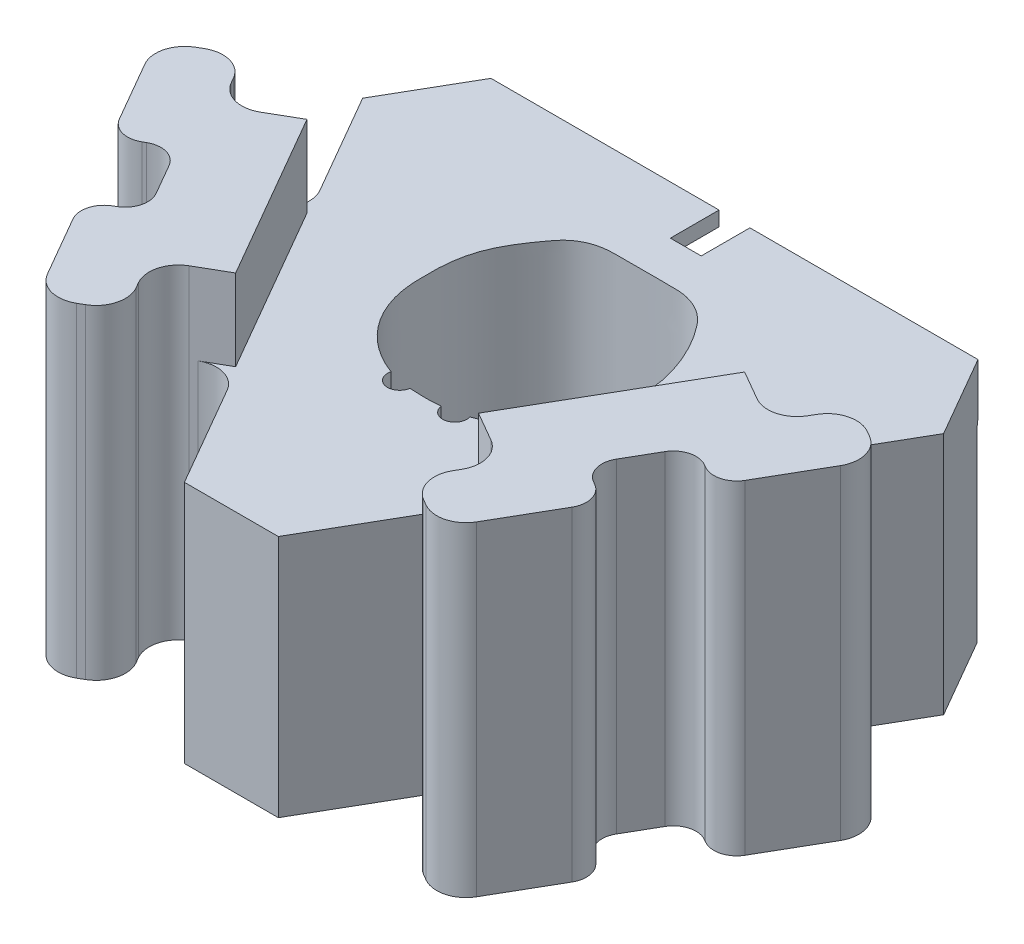
SolidWorks part; units mm, degrees
material "Nylon 101"
ref_plane "Plan de face" through (0, 0, 0) normal (0, 0, 1) x (1, 0, 0)
ref_plane "Plan de dessus" through (0, 0, 0) normal (0, 1, 0) x (1, 0, 0)
ref_plane "Plan de droite" through (0, 0, 0) normal (1, 0, 0) x (0, 0, -1)
sketch "Esquisse2" plane through (0, 0, 0) normal (0, 1, 0) x (1, 0, 0)
  line L5 (0, 0) -> (0, 12) construction
  line L6 (15, 12) -> (-15, 12)
  line L10 (2.8923, -18.9904) -> (17.8923, 6.9904)
  line L11 (0, 0) -> (10.3923, -6) construction
  line L12 (-17.8923, 6.9904) -> (-2.8923, -18.9904)
  line L13 (0, 0) -> (-10.3923, -6) construction
  line L14 (-15, 12) -> (-17.8923, 6.9904)
  line L15 (-2.8923, -18.9904) -> (2.8923, -18.9904)
  line L16 (17.8923, 6.9904) -> (15, 12)
  circle A0 centre (0, 0) radius 6.4543 construction
  spline S0 degree 3 poles (-6.4916, -0.6583) (-6.5698, 2.1101) (-5.6306, 3.6458) (-3.9015, 5.9899) (-2.756, 6.4428) (-0.8765, 6.4556) (1.1323, 6.4563) (2.7646, 6.4372) (3.9155, 5.9368) (5.686, 3.7258) (6.557, 1.3673) (6.4965, -0.4633) (6.5146, -1.1319) (6.2478, -3.8936) (4.3275, -6.6394) (0.5445, -7.077) (-0.4227, -7.0644) (-3.089, -6.9353) (-6.1206, -4.861) (-6.5148, -1.2298) (-6.4916, -0.6583) (-6.5698, 2.1101) (-5.6306, 3.6458) knots -0.028087 -0.008777 -0.000975 0 0.112372 0.130276 0.173621 0.187169 0.252205 0.26694 0.319781 0.34342 0.479691 0.498677 0.514296 0.542967 0.756721 0.785787 0.80456 0.825241 0.971913 0.991223 0.999025 1 1.112372 1.130276 1.173621 only from (-6.4978, -0.4355) to (-6.4978, -0.4355)
  point P6 (0, 12)
  point P15 (0, 0)
  dimension "D1" = 30
  dimension "D2" = 3
  dimension "D3" = 12
extrude "Boss.-Extru.1" add sketch "Esquisse2" along normal blind 15
sketch "Esquisse3" plane through (0, 0, 0) normal (0, 1, 0) x (1, 0, 0)
  line L0 (0, 0) -> (3.3, 0) construction
  line L1 (0, 0) -> (0, 3.3) construction
  line L2 (-16.4462, 9.4952) -> (0, 0) construction
  line L5 (-17.8923, 6.9904) -> (-15, 12) construction
  line L6 (0, 0) -> (16.4462, 9.4952) construction
  line L7 (15, 12) -> (17.8923, 6.9904) construction
  line L8 (0, 0) -> (0, -18.9904) construction
  line L9 (2.8923, -18.9904) -> (-2.8923, -18.9904) construction
  circle A0 centre (0, 0) radius 3.3 construction
  circle A5 centre (-12.9821, 7.4952) radius 2
  circle A7 centre (12.9821, 7.4952) radius 2
  circle A8 centre (0, -14.9904) radius 2
  point P23 (0, 0)
  dimension "D1" = 6.6
  dimension "D3" = 4
  dimension "D2" = 4
  dimension "D4" = 3
extrude "Enlèv. mat.-Extru.3" [suppressed] cut sketch "Esquisse3" against normal blind 8 and the other way through all from surface starting at face at (0, 15, 0)
sketch "Esquisse4" plane through (0, 0, 0) normal (0, 0, 1) x (1, 0, 0)
  line L0 (0, 0) -> (0, 7) construction
  line L1 (11, 3) -> (-11, 3) construction
  line L2 (11, 3) -> (11, 11) construction
  line L3 (11, 11) -> (-11, 11) construction
  line L4 (-11, 3) -> (-11, 11) construction
  line L5 (11, 3) -> (-11, 11) construction
  line L6 (11, 11) -> (-11, 3) construction
  line L8 (-17.8923, 0) -> (-2.8923, 0) construction
  circle A0 centre (-11, 11) radius 1.5
  circle A1 centre (11, 11) radius 1.5
  circle A2 centre (11, 3) radius 1.5
  circle A3 centre (-11, 3) radius 1.5
  point P0 (0, 7)
  dimension "D4" = 3
  dimension "D1" = 8
  dimension "D2" = 22
  dimension "D3" = 3
extrude "Enlèv. mat.-Extru.4" cut sketch "Esquisse4" along normal blind 8 from surface starting at face at (0, 7.5, -12)
sketch "Esquisse5" plane through (0, 0, 0) normal (0, 1, 0) x (1, 0, 0)
  line L0 (0, 0) -> (0, -18.9904) construction
  line L1 (2.8923, -18.9904) -> (-2.8923, -18.9904) construction
  line L2 (10.3923, -6) -> (17.3205, -10) construction
  line L3 (17.8923, 6.9904) -> (2.8923, -18.9904) construction
  line L4 (13.2205, -17.1014) -> (15.3705, -13.3775)
  line L5 (20.7617, -0.4397) -> (20.4153, -0.2397)
  line L6 (17.9564, -0.8986) -> (17.7564, -1.245)
  line L7 (15.2976, -1.9038) -> (13.3923, -0.8038)
  line L8 (13.3923, -0.8038) -> (7.3923, -11.1962)
  line L9 (9.2976, -12.2962) -> (7.3923, -11.1962)
  line L10 (9.7564, -15.1014) -> (9.9564, -14.755)
  line L11 (10.7617, -17.7603) -> (10.4153, -17.5603)
  line L12 (20.7617, -0.4397) -> (20.4153, -0.2397)
  line L13 (17.9564, -0.8986) -> (17.7564, -1.245)
  line L14 (15.2976, -1.9038) -> (13.3923, -0.8038)
  line L15 (9.2976, -12.2962) -> (7.3923, -11.1962)
  line L16 (9.7564, -15.1014) -> (9.9564, -14.755)
  line L17 (10.7617, -17.7603) -> (10.4153, -17.5603)
  line L18 (-17.3205, -10) -> (-18.5705, -7.8349) construction
  line L19 (-16.0705, -12.1651) -> (-17.3205, -10) construction
  line L20 (-10.3923, -6) -> (-17.3205, -10) construction
  line L21 (-19.2705, -6.6225) -> (-21.4205, -2.8986)
  line L22 (-17.1849, -7.0349) -> (-17.3581, -7.1349)
  line L23 (-14.1724, -9.4526) -> (-15.2724, -7.5474)
  line L24 (-14.8581, -11.4651) -> (-14.6849, -11.3651)
  line L25 (-10.7617, -17.7603) -> (-10.4153, -17.5603)
  line L26 (-9.7564, -15.1014) -> (-9.9564, -14.755)
  line L27 (-9.2976, -12.2962) -> (-7.3923, -11.1962)
  line L28 (-15.2976, -1.9038) -> (-13.3923, -0.8038)
  line L29 (-17.9564, -0.8986) -> (-17.7564, -1.245)
  line L30 (-20.7617, -0.4397) -> (-20.4153, -0.2397)
  line L31 (-10.7617, -17.7603) -> (-10.4153, -17.5603)
  line L32 (-9.7564, -15.1014) -> (-9.9564, -14.755)
  line L33 (14.8581, -11.4651) -> (14.6849, -11.3651)
  line L34 (14.1724, -9.4526) -> (15.2724, -7.5474)
  line L35 (17.1849, -7.0349) -> (17.3581, -7.1349)
  line L36 (16.0705, -12.1651) -> (17.3205, -10) construction
  line L37 (19.2705, -6.6225) -> (21.4205, -2.8986)
  line L38 (17.3205, -10) -> (18.5705, -7.8349) construction
  line L39 (-9.2976, -12.2962) -> (-7.3923, -11.1962)
  line L40 (-13.3923, -0.8038) -> (-7.3923, -11.1962)
  line L41 (-15.2976, -1.9038) -> (-13.3923, -0.8038)
  line L42 (-17.9564, -0.8986) -> (-17.7564, -1.245)
  line L43 (-20.7617, -0.4397) -> (-20.4153, -0.2397)
  line L44 (-13.2205, -17.1014) -> (-15.3705, -13.3775)
  arc A0 (10.7617, -17.7603) -> (13.2205, -17.1014) centre (11.6617, -16.2014) ccw
  arc A1 (9.7564, -15.1014) -> (10.4153, -17.5603) centre (11.3153, -16.0014) ccw
  arc A2 (9.2976, -12.2962) -> (9.9564, -14.755) centre (8.3976, -13.855) cw
  arc A3 (21.4205, -2.8986) -> (20.7617, -0.4397) centre (19.8617, -1.9986) ccw
  arc A4 (17.7564, -1.245) -> (15.2976, -1.9038) centre (16.1976, -0.345) cw
  arc A5 (20.4153, -0.2397) -> (17.9564, -0.8986) centre (19.5153, -1.7986) ccw
  arc A6 (10.4153, -17.5603) -> (9.7564, -15.1014) centre (11.3153, -16.0014) cw
  arc A7 (9.9564, -14.755) -> (9.2976, -12.2962) centre (8.3976, -13.855) ccw
  arc A8 (13.2205, -17.1014) -> (10.7617, -17.7603) centre (11.6617, -16.2014) cw
  arc A9 (15.2976, -1.9038) -> (17.7564, -1.245) centre (16.1976, -0.345) ccw
  arc A10 (17.9564, -0.8986) -> (20.4153, -0.2397) centre (19.5153, -1.7986) cw
  arc A11 (20.7617, -0.4397) -> (21.4205, -2.8986) centre (19.8617, -1.9986) cw
  arc A24 (17.3581, -7.1349) -> (19.2705, -6.6225) centre (18.0581, -5.9225) ccw
  arc A25 (15.2724, -7.5474) -> (17.1849, -7.0349) centre (16.4849, -8.2474) cw
  arc A26 (14.6849, -11.3651) -> (14.1724, -9.4526) centre (15.3849, -10.1526) cw
  arc A27 (14.8581, -11.4651) -> (15.3705, -13.3775) centre (14.1581, -12.6775) cw
  arc A28 (-14.8581, -11.4651) -> (-15.3705, -13.3775) centre (-14.1581, -12.6775) ccw
  arc A29 (-14.6849, -11.3651) -> (-14.1724, -9.4526) centre (-15.3849, -10.1526) ccw
  arc A30 (-15.2724, -7.5474) -> (-17.1849, -7.0349) centre (-16.4849, -8.2474) ccw
  arc A31 (-17.3581, -7.1349) -> (-19.2705, -6.6225) centre (-18.0581, -5.9225) cw
  arc A32 (-20.7617, -0.4397) -> (-21.4205, -2.8986) centre (-19.8617, -1.9986) ccw
  arc A33 (-17.9564, -0.8986) -> (-20.4153, -0.2397) centre (-19.5153, -1.7986) ccw
  arc A34 (-15.2976, -1.9038) -> (-17.7564, -1.245) centre (-16.1976, -0.345) cw
  arc A35 (-13.2205, -17.1014) -> (-10.7617, -17.7603) centre (-11.6617, -16.2014) ccw
  arc A36 (-9.9564, -14.755) -> (-9.2976, -12.2962) centre (-8.3976, -13.855) cw
  arc A37 (-10.4153, -17.5603) -> (-9.7564, -15.1014) centre (-11.3153, -16.0014) ccw
  arc A38 (-20.4153, -0.2397) -> (-17.9564, -0.8986) centre (-19.5153, -1.7986) cw
  arc A39 (-17.7564, -1.245) -> (-15.2976, -1.9038) centre (-16.1976, -0.345) ccw
  arc A40 (-21.4205, -2.8986) -> (-20.7617, -0.4397) centre (-19.8617, -1.9986) cw
  arc A41 (-9.2976, -12.2962) -> (-9.9564, -14.755) centre (-8.3976, -13.855) ccw
  arc A42 (-9.7564, -15.1014) -> (-10.4153, -17.5603) centre (-11.3153, -16.0014) cw
  arc A43 (-10.7617, -17.7603) -> (-13.2205, -17.1014) centre (-11.6617, -16.2014) cw
  point P19 (12.3205, -18.6603)
  point P22 (8.8564, -16.6603)
  point P25 (10.8564, -13.1962)
  point P28 (22.3205, -1.3397)
  point P31 (16.8564, -2.8038)
  point P34 (18.8564, 0.6603)
  point P64 (14.7224, -8.5)
  point P72 (15.9724, -6.3349)
  point P75 (13.4724, -10.6651)
  point P88 (-13.4724, -10.6651)
  point P89 (-15.9724, -6.3349)
  point P90 (-18.8564, 0.6603)
  point P91 (-16.8564, -2.8038)
  point P92 (-22.3205, -1.3397)
  point P93 (-10.8564, -13.1962)
  point P94 (-8.8564, -16.6603)
  point P95 (-12.3205, -18.6603)
  dimension "D5" = 1.8
  dimension "D8" = 1.4
  dimension "D1" = 8
  dimension "D2" = 4
  dimension "D3" = 4
  dimension "D4" = 10
  dimension "D6" = 3
  dimension "D7" = 5
extrude "Boss.-Extru.2" add sketch "Esquisse5" against normal up to surface and the other way blind 5 from surface contours L5 A5 L6 A4 L7 L8 L9 A2 L10 A1 L11 A0 L4 A3 | L25 A37 L26 A36 L27 L40 L28 A34 L29 A33 L30 A32 L21 A31 L22 A30 L23 A29 L24 A28 L44 A35 region at (13.999, 0, 8.0823) region at (-13.999, 0, 8.0823) up to face at (0, 0, 0) starting at face at (0, 15, 0)
fillet "Congé5" radius 1.8 4 edges at (13.3923, 7.5, 0.8038) (7.3923, 7.5, 11.1962) (-7.3923, 7.5, 11.1962) (-13.3923, 7.5, 0.8038)
sketch "Esquisse6" plane through (0, 0, 0) normal (0, 1, 0) x (1, 0, 0)
  line L0 (-13.3923, -0.8038) -> (-7.3923, -11.1962)
  line L1 (-7.3923, -11.1962) -> (-7.4789, -11.2462)
  line L2 (-7.3923, -11.1962) -> (-9.2976, -12.2962) construction
  line L3 (-7.4789, -11.2462) -> (-13.4789, -0.8538)
  line L4 (-13.3923, -0.8038) -> (-15.2976, -1.9038) construction
  line L5 (-13.4789, -0.8538) -> (-13.3923, -0.8038)
  line L6 (7.3923, -11.1962) -> (13.3923, -0.8038)
  line L7 (13.3923, -0.8038) -> (13.4789, -0.8538)
  line L8 (14.9512, -1.7038) -> (13.3923, -0.8038) construction
  line L9 (13.4789, -0.8538) -> (7.4789, -11.2462)
  line L10 (7.3923, -11.1962) -> (9.2976, -12.2962) construction
  line L11 (7.4789, -11.2462) -> (7.3923, -11.1962)
  dimension "D1" = 0.1
  dimension "D2" = 0.1
extrude "Enlèv. mat.-Extru.5" cut sketch "Esquisse6" along normal up to surface (20 mm away) from surface up to face at (-14.8463, 20, 8.5715) starting at face at (0, 15, 4.1586)
sketch "Esquisse7" plane through (0, 0, -12) normal (0, 0, -1) x (-1, 0, 0)
  line L0 (15, 15) -> (15, 0) construction
  line L1 (-15, 0) -> (15, 0) construction
  line L2 (-15, 0) -> (-15, 14) construction
  line L3 (-15, 14) -> (-0.85, 14) construction
  line L4 (15, 0) -> (15, 14) construction
  line L5 (-15, 15) -> (15, 15) construction
  line L6 (0.85, 0) -> (-0.85, 0)
  line L7 (0.85, 14) -> (0.85, 15) construction
  line L8 (0.85, 15) -> (-0.85, 15) construction
  line L9 (-0.85, 14) -> (-0.85, 15) construction
  line L10 (-0.85, 0) -> (-0.85, 14) construction
  line L11 (0.85, 0) -> (0.85, 14) construction
  line L12 (-0.85, 14) -> (0.85, 14) construction
  line L13 (0.85, 14) -> (15, 14) construction
  line L14 (-15.1, -0.1) -> (-15.1, 14.1)
  line L15 (-15.1, 14.1) -> (-0.95, 14.1)
  line L16 (-0.95, 14.1) -> (-0.95, 15.1)
  line L17 (0.95, 15.1) -> (-0.95, 15.1)
  line L18 (0.95, 14.1) -> (0.95, 15.1)
  line L19 (0.95, 14.1) -> (15.1, 14.1)
  line L20 (15.1, -0.1) -> (15.1, 14.1)
  line L21 (-15.1, -0.1) -> (15.1, -0.1)
  circle A0 centre (11, 11) radius 1.5 construction
  circle M9 centre (-11, 3) radius 1.5
  circle M10 centre (11, 11) radius 1.5
  circle M11 centre (11, 3) radius 1.5
  circle M12 centre (-11, 11) radius 1.5
  line M13 (-15, 0) -> (15, 0)
  line M14 (15, 0) -> (15, 15)
  line M15 (15, 15) -> (-15, 15)
  line M16 (-15, 15) -> (-15, 0)
  dimension "D1" = 3
  dimension "D2" = 0.85
  dimension "D3" = 0.85
  dimension "D4" = 0.1
extrude "Enlèv. mat.-Extru.6" cut sketch "Esquisse7" against normal blind 3 contours L14 L21 L20 L19 L15 M14 M13 M16 | L19 L18 L16 L15 M15 M16 M13 M14 M10 M12 M11 M9 | L18 L17 L16 M15 region at (-7.925, -0.0334, -12) region at (0, 7.0859, -12) region at (0, 15.05, -12)
fillet "Congé6" radius 3 2 edges at (-15.1, 14.1, -10.4134) (15.1, 14.1, -10.4134)
sketch "Esquisse8" plane through (0, 15, 0) normal (0, 1, 0) x (1, 0, 0)
  line L0 (0, 0) -> (0, -2.8854) construction
  circle A0 centre (-1.7, -6.9242) radius 0.75
  circle A1 centre (1.7, -6.9242) radius 0.75
  spline S0 degree 3 poles (-5.6306, 3.6458) (-6.5698, 2.1101) (-6.4916, -0.6583) (-6.5148, -1.2298) (-6.1206, -4.861) (-3.089, -6.9353) (-0.4227, -7.0644) (0.5445, -7.077) (4.3275, -6.6394) (6.2478, -3.8936) (6.5146, -1.1319) (6.4965, -0.4633) (6.557, 1.3673) (5.686, 3.7258) (3.9155, 5.9368) (2.7646, 6.4372) (1.1323, 6.4563) (-0.8765, 6.4556) (-2.756, 6.4428) (-3.9015, 5.9899) (-5.6306, 3.6458) (-6.5698, 2.1101) (-6.4916, -0.6583) knots -0.173621 -0.130276 -0.112372 0 0.000975 0.008777 0.028087 0.174759 0.19544 0.214213 0.243279 0.457033 0.485704 0.501323 0.520309 0.65658 0.680219 0.73306 0.747795 0.812831 0.826379 0.869724 0.887628 1 1.000975 1.008777 1.028087 only from (-6.4978, -0.4355) to (-6.4978, -0.4355) construction
  point P2 (0, 0)
  dimension "D2" = 1.5
  dimension "D1" = 1.7
extrude "Enlèv. mat.-Extru.7" cut sketch "Esquisse8" against normal through all
